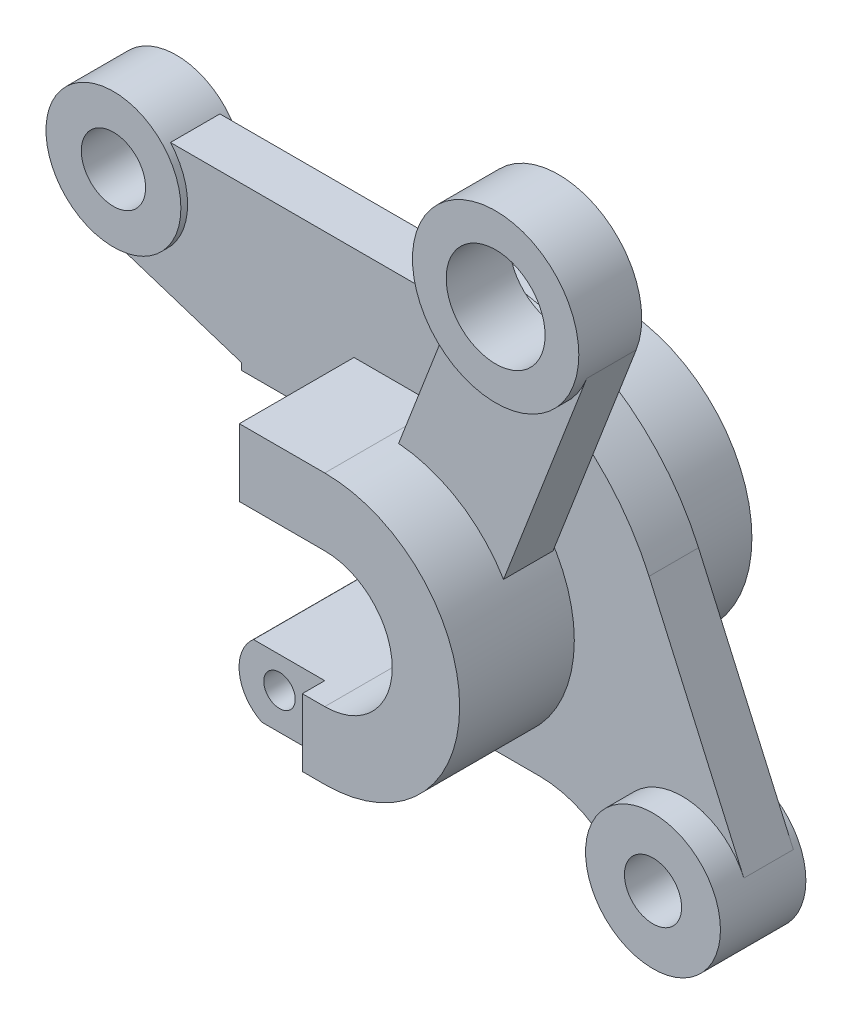
SolidWorks part; units mm, degrees
ref_plane "Front Plane" through (0, 0, 0) normal (0, 0, 1) x (1, 0, 0)
ref_plane "Top Plane" through (0, 0, 0) normal (0, 1, 0) x (1, 0, 0)
ref_plane "Right Plane" through (0, 0, 0) normal (1, 0, 0) x (0, 0, -1)
sketch "Sketch1" plane through (0, 0, 0) normal (0, 0, 1) x (1, 0, 0)
  line L0 (1039.6569, 0) -> (19.8285, 0) construction
  line L1 (0, 1060) -> (0, 30) construction
  line L2 (0, 30) -> (-19, 30)
  line L3 (0, -30) -> (-19, -30)
  line L4 (0, 15) -> (-19, 15)
  line L5 (0, -15) -> (-20.8395, -15)
  line L6 (-19, 30) -> (-19, 15)
  line L8 (-5, -15) -> (-5, -30)
  line L9 (46.6269, 20.6623) -> (67.7138, -26.9229)
  line L10 (0, 51) -> (-59.8197, 51)
  line L11 (0, -30) -> (22.251, -30)
  line L12 (0, 0) -> (27, 70) construction
  line L13 (44.2605, 63.3424) -> (25.7595, 15.3768)
  line L15 (15, 0) -> (-33144.7884, 0) construction
  line L16 (-19, 15) -> (-44, 15)
  line L17 (0, 15) -> (0, -33144.7884) construction
  line L18 (-44, 15) -> (-44, 16.5)
  line L19 (-44, 16.5) -> (-75.617, 26.7282)
  line L20 (13.1562, 57.7281) -> (2.4232, 29.902)
  arc A0 (0, -15) -> (0, 15) centre (0, 0) ccw
  arc A1 (0, -30) -> (0, 30) centre (0, 0) ccw
  arc A2 (-19, -30) -> (-20.8395, -15) centre (-15.0669, -21.9049) cw
  circle A3 centre (-15.0669, -21.9049) radius 3.5
  circle A4 centre (54, -33) radius 6.355
  circle A5 centre (54, -33) radius 15
  circle A6 centre (27, 70) radius 11
  circle A7 centre (27, 70) radius 18.5
  circle A8 centre (-71, 41) radius 15
  circle A9 centre (-71, 41) radius 7.1475
  arc A10 (46.6269, 20.6623) -> (0, 51) centre (0, 0) ccw
  arc A11 (41.1288, -40.7027) -> (22.251, -30) centre (22.251, -52) ccw
  point P17 (-24, -23.0004)
  dimension "D1" = 60
  dimension "D2" = 30
  dimension "D5" = 9
  dimension "D6" = 19
  dimension "D7" = 7
  dimension "D8" = 12.71
  dimension "D9" = 30
  dimension "D12" = 37
  dimension "D13" = 22
  dimension "D16" = 30
  dimension "D17" = 14.295
  dimension "D20" = 102
  dimension "D21" = 44
  dimension "D3" = 19
  dimension "D4" = 5
  dimension "D10" = 54
  dimension "D11" = 33
  dimension "D14" = 70
  dimension "D15" = 27
  dimension "D18" = 71
  dimension "D19" = 41
  dimension "D22" = 27
  dimension "D23" = 25
  dimension "D24" = 1.5
extrude "Boss-Extrude1" add sketch "Sketch1" against normal blind 65 contours A1 L2 L6 L4 A0 L5 L8 L3 region at (1.1813, 29.2015, 0)
extrude "Boss-Extrude2" add sketch "Sketch1<4>" against normal blind 14 from offset 11 separate body contours A7 A6 region at (20.6229, 86.8076, 0) offset against normal yes
sketch "Sketch1<4>" plane through (0, 0, 0) normal (0, 0, 1) x (1, 0, 0) same geometry as "Sketch1"
extrude "Boss-Extrude3" add sketch "Sketch1<5>" against normal blind 19 from offset 19 separate body contours A5 A4 region at (68.2599, -29.982, 0) offset against normal yes
sketch "Sketch1<5>" plane through (0, 0, 0) normal (0, 0, 1) x (1, 0, 0) same geometry as "Sketch1"
extrude "Boss-Extrude4" add sketch "Sketch1<6>" against normal blind 14 from offset 24 separate body contours A8 A9 region at (-57.3838, 46.2009, 0) offset against normal yes
sketch "Sketch1<6>" plane through (0, 0, 0) normal (0, 0, 1) x (1, 0, 0) same geometry as "Sketch1"
extrude "Boss-Extrude5" add sketch "Sketch1<7>" against normal blind 11 from offset 25.5 contours L20 A10 L10 A8 L19 L18 L16 L6 L2 A1 region at (-29.8836, 35.3244, 0) offset against normal yes
sketch "Sketch1<7>" plane through (0, 0, 0) normal (0, 0, 1) x (1, 0, 0) same geometry as "Sketch1"
extrude "Boss-Extrude6" add sketch "Sketch1<8>" against normal blind 11 from offset 25.5 contours A11 A5 L9 A10 L13 A1 L11 | L13 A10 L20 A1 region at (19.0065, 34.7532, 0) region at (39.0273, -3.3999, 0) offset against normal yes
sketch "Sketch1<8>" plane through (0, 0, 0) normal (0, 0, 1) x (1, 0, 0) same geometry as "Sketch1"
extrude "Boss-Extrude8" add sketch "Sketch1<9>" against normal blind 11 from offset 14 contours L13 A10 L20 A1 | A10 L13 A7 L20 region at (19.0065, 34.7532, 0) region at (27.5648, 48.865, 0) offset against normal yes
sketch "Sketch1<9>" plane through (0, 0, 0) normal (0, 0, 1) x (1, 0, 0) same geometry as "Sketch1"
extrude "Boss-Extrude9" add sketch "Sketch1<11>" against normal blind 55 from offset 5 contours A2 L3 L8 L5 A3 region at (-12, -29.7574, 0) offset against normal yes
sketch "Sketch1<11>" plane through (0, 0, 0) normal (0, 0, 1) x (1, 0, 0) same geometry as "Sketch1"
